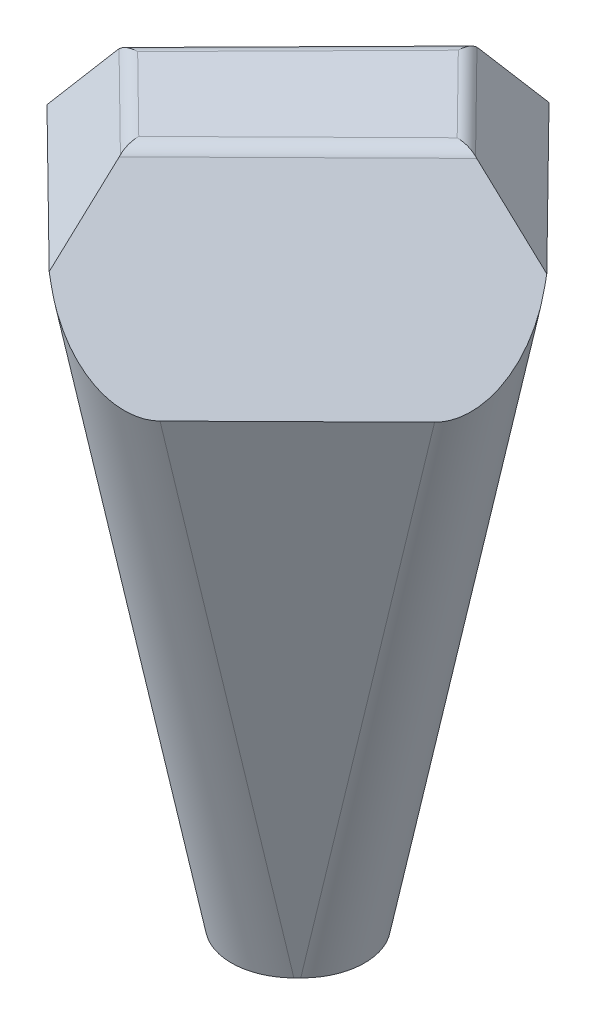
SolidWorks part; units mm, degrees
ref_plane "Front Plane" through (0, 0, 0) normal (0, 0, 1) x (1, 0, 0)
ref_plane "Top Plane" through (0, 0, 0) normal (0, 1, 0) x (1, 0, 0)
ref_plane "Right Plane" through (0, 0, 0) normal (1, 0, 0) x (0, 0, -1)
sketch "Sketch3" plane through (0, 0, 0) normal (0, 0, 1) x (1, 0, 0)
  line L1 (-25.4, -57.15) -> (25.4, -57.15)
  line L2 (-25.4, -57.15) -> (-25.4, 57.15)
  line L3 (-25.4, 57.15) -> (25.4, 57.15)
  line L4 (25.4, -57.15) -> (25.4, 57.15)
  line L5 (-25.4, -57.15) -> (25.4, 57.15) construction
  line L6 (-25.4, 57.15) -> (25.4, -57.15) construction
  point P0 (0, 0)
  dimension "D1" = 50.8
  dimension "D2" = 114.3
extrude "Boss-Extrude5" add sketch "Sketch3" along normal blind 50.8
ref_plane "Plane2" through (0, -59.69, 0) normal (0, -1, 0) x (-1, 0, 0)
sketch "Sketch6" plane through (0, -59.69, 0) normal (0, -1, 0) x (-1, 0, 0)
  line L1 (49.8815, -94.9815) -> (-58.6272, -94.9815)
  line L2 (49.8815, -94.9815) -> (49.8815, 9.1068)
  line L3 (49.8815, 9.1068) -> (-58.6272, 9.1068)
  line L4 (-58.6272, -94.9815) -> (-58.6272, 9.1068)
  line L5 (49.8815, -94.9815) -> (-58.6272, 9.1068) construction
  line L6 (49.8815, 9.1068) -> (-58.6272, -94.9815) construction
  point P0 (-4.3729, -42.9374)
draft "Draft2" type of draft neutral plane draft angle 7 faces to draft 4 face at (0, 0, 50.8) face at (25.4, 0, 25.4) face at (0, 0, 0) face at (-25.4, 0, 25.4) neutral plane through (-25.4, -57.15, 50.8) neutral plane normal (0, -1, 0) parameters "D1"=7
chamfer "Chamfer22" distance 35.56 angle 45 4 edges at (32.4171, 0, 57.8171) (32.4171, 0, -7.0171) (-32.4171, 0, 57.8171) (-32.4171, 0, -7.0171)
chamfer "Chamfer26" distance 12.7 angle 45 2 edges at (21.5227, 57.15, 4.1493) (-21.2507, 57.15, 46.9227)
chamfer "Chamfer27" distance 20.32 angle 60 1 edges at (21.3869, 57.15, 46.7885)
chamfer "Chamfer28" distance 20.32 angle 65 1 edges at (-21.3869, 57.15, 4.0115)
fillet "Fillet36" radius 2.54 4 edges at (-7.0181, 57.15, 18.3803) (7.0181, 57.15, 32.4197) (-13.621, 57.15, 39.0218) (13.621, 57.15, 11.7782)
fillet "Fillet41" radius 10.16 4 edges at (0, -13.5288, 50.6287) (0, -15.8763, 0.3689) (25.4006, -13.5974, 25.5915) (-24.841, -15.8763, 25.5872)
shell "Shell2" thickness 1.27
